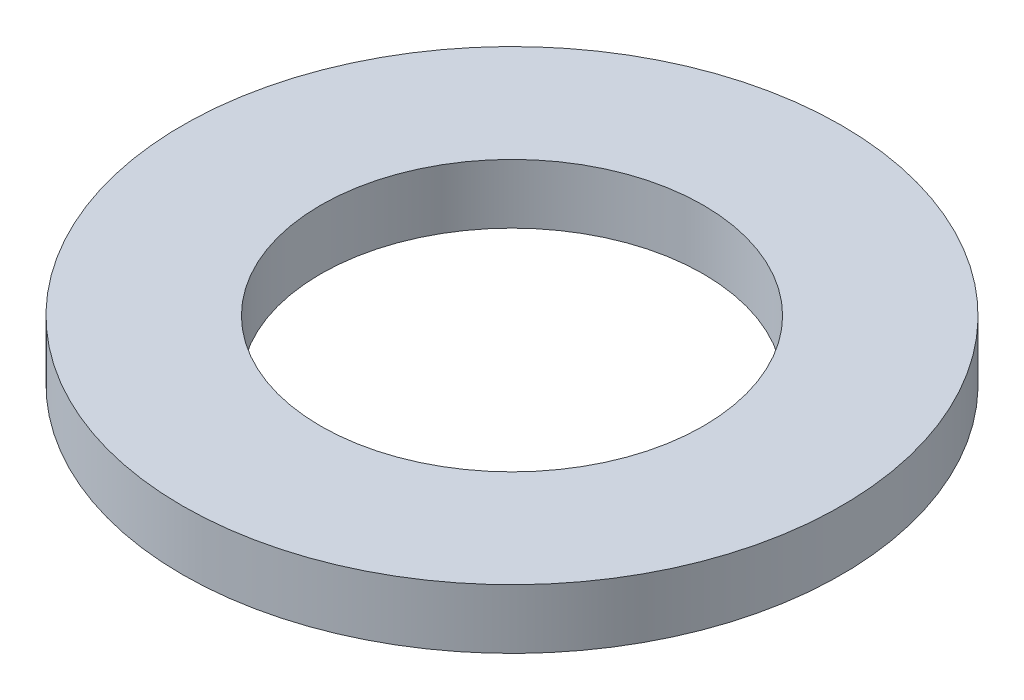
SolidWorks part; units mm, degrees
ref_plane "Front Plane" through (0, 0, 0) normal (0, 0, 1) x (1, 0, 0)
ref_plane "Top Plane" through (0, 0, 0) normal (0, 1, 0) x (1, 0, 0)
ref_plane "Right Plane" through (0, 0, 0) normal (1, 0, 0) x (0, 0, -1)
sketch "Sketch1" plane through (0, 0, 0) normal (0, 1, 0) x (1, 0, 0)
  circle A0 centre (0, 0) radius 77.5
  dimension "FLANGE_OD" = 155
extrude "Boss-Extrude1" add sketch "Sketch1" along normal blind 14
sketch "Sketch2" plane through (0, 0, 0) normal (0, 1, 0) x (1, 0, 0)
  circle A0 centre (0, 0) radius 45
  dimension "BORE_D" = 90
extrude "Cut-Extrude1" cut sketch "Sketch2" along normal through all
sketch "Sketch3" plane through (0, 14, 0) normal (0, 1, 0) x (1, 0, 0)
  circle A0 centre (0, 0) radius 32.8966 construction
  circle A1 centre (-32.8966, 0) radius 3.2307
  dimension "BOLT_D" = 6.4615
  dimension "BOLT_PCD" = 65.7933
extrude "Cut-Extrude2" cut sketch "Sketch3" against normal blind 9.0151 rebuild error yes
pattern_circular "CirPattern1" count 3 over 360 rebuild error yes
